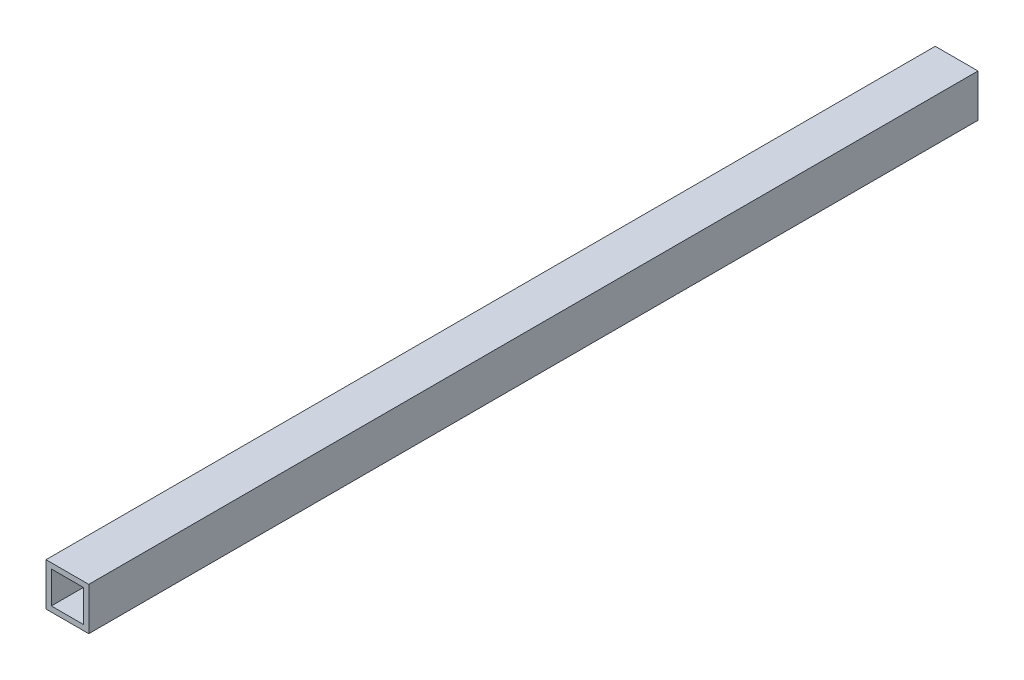
SolidWorks part; units mm, degrees
material "6061 Alloy"
ref_plane "Front Plane" through (0, 0, 0) normal (0, 0, 1) x (1, 0, 0)
ref_plane "Top Plane" through (0, 0, 0) normal (0, 1, 0) x (1, 0, 0)
ref_plane "Right Plane" through (0, 0, 0) normal (1, 0, 0) x (0, 0, -1)
sketch "Sketch1" plane through (0, 0, 0) normal (0, 0, 1) x (1, 0, 0)
  line L0 (12.7, 0) -> (9.525, 0) construction
  line L1 (-12.7, 0) -> (12.7, 0) construction
  line L2 (0, 12.7) -> (0, -12.7)
  point P7 (0, 0)
sketch "Sketch2" plane through (0, 0, 0) normal (1, 0, 0) x (0, 0, -1)
  line L0 (264.16, 0) -> (-264.16, 0)
  point P4 (0, 0)
  dimension "Length" = 528.32
sketch "Sketch3" plane through (0, 0, 0) normal (0, 0, 1) x (1, 0, 0)
  line L0 (-12.7, 0) -> (12.7, 0) construction
  line L5 (12.7, -12.7) -> (-12.7, -12.7)
  line L6 (12.7, -12.7) -> (12.7, 12.7)
  line L11 (12.7, 12.7) -> (-12.7, 12.7)
  line L12 (-12.7, -12.7) -> (-12.7, 12.7)
  line L14 (12.7, -12.7) -> (-12.7, 12.7) construction
  line L15 (12.7, 12.7) -> (-12.7, -12.7) construction
  line L16 (9.525, -9.525) -> (-9.525, -9.525)
  line L17 (9.525, -9.525) -> (9.525, 9.525)
  line L18 (9.525, 9.525) -> (-9.525, 9.525)
  line L19 (-9.525, -9.525) -> (-9.525, 9.525)
  line L20 (9.525, -9.525) -> (-9.525, 9.525) construction
  line L21 (9.525, 9.525) -> (-9.525, -9.525) construction
  point P0 (0, 0)
  point P5 (0, 0)
  point P13 (9.525, -12.7)
  dimension "D1" = 3.175
extrude "Boss-Extrude1" add sketch "Sketch3" along normal up to vertex (264.16 mm away) and the other way up to vertex (264.16 mm away) up to point (0, 0, 264.16) other way up to point (0, 0, -264.16)
sketch "Sketch5" plane through (0, 0, 0) normal (1, 0, 0) x (0, 0, -1)
  line L0 (-264.16, 0) -> (264.16, 0) construction
  line L3 (-264.16, -12.7) -> (-264.16, 12.7) construction
  line L4 (264.16, -12.7) -> (264.16, 12.7) construction
  point P6 (-235.585, 0)
  point P7 (-226.06, 0)
  point P8 (226.06, 0)
  point P10 (235.585, 0)
  dimension "D1" = 28.575
  dimension "D2" = 38.1
  dimension "D3" = 28.575
  dimension "D4" = 38.1
equation "\"D1@Sketch3\"=\"Wall thickness@Sketch1\""
equation "\"D1@Sketch5\"=\"Width@Sketch1\"*1.125"
equation "\"D2@Sketch5\"=\"Width@Sketch1\"*1.5"
equation "\"D3@Sketch5\"=\"D1@Sketch5\""
equation "\"D4@Sketch5\"=\"D2@Sketch5\""
equation "\"D2@Sketch3\"=\"Wall Thickness@Sketch1\""
